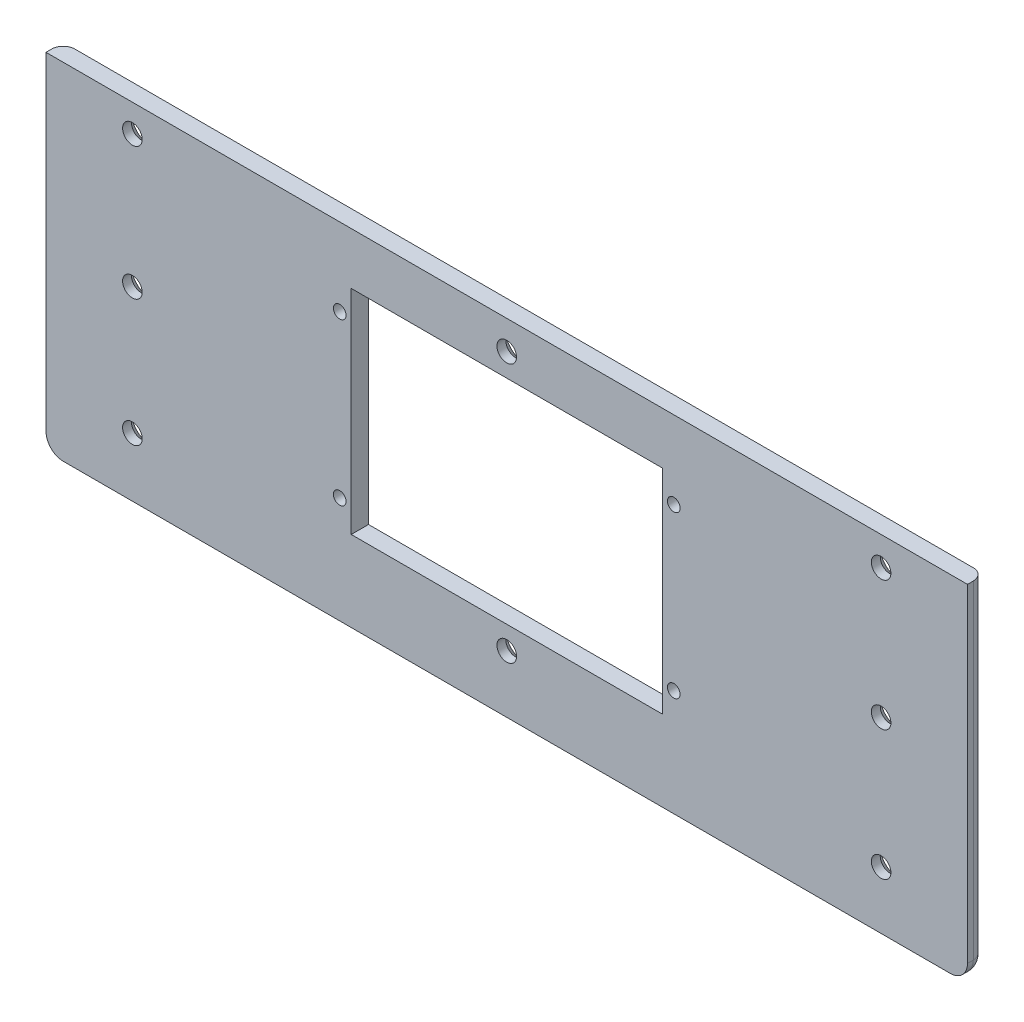
SolidWorks part; units mm, degrees
ref_plane "Front Plane" through (0, 0, 0) normal (0, 0, 1) x (1, 0, 0)
ref_plane "Top Plane" through (0, 0, 0) normal (0, 1, 0) x (1, 0, 0)
ref_plane "Right Plane" through (0, 0, 0) normal (1, 0, 0) x (0, 0, -1)
sketch "Sketch1" plane through (0, 0, 0) normal (0, 0, 1) x (1, 0, 0)
  line L1 (0, 0) -> (160, 0)
  line L2 (0, 0) -> (0, 60)
  line L3 (0, 60) -> (160, 60)
  line L4 (160, 0) -> (160, 60)
  dimension "D1" = 160
  dimension "D2" = 60
extrude "Boss-Extrude1" add sketch "Sketch1" along normal blind 3
sketch "Sketch2" plane through (0, 0, 0) normal (0, 0, -1) x (-1, 0, 0)
  line L0 (-53.5, 14.5) -> (-53.5, 50.5) construction
  line L1 (-106.5, 14.5) -> (-53.5, 14.5) construction
  line L2 (-106.5, 50.5) -> (-106.5, 14.5) construction
  line L3 (-53.5, 50.5) -> (-106.5, 50.5) construction
  line L4 (-53.5, 14.5) -> (-53.5, 50.5) construction
  line L5 (-106.5, 14.5) -> (-53.5, 14.5) construction
  line L6 (-106.5, 50.5) -> (-106.5, 14.5) construction
  line L7 (-53.5, 50.5) -> (-106.5, 50.5) construction
  line L9 (-107, 51) -> (-53, 51)
  line L10 (-107, 51) -> (-107, 14)
  line L11 (-107, 14) -> (-53, 14)
  line L12 (-53, 51) -> (-53, 14)
  circle A0 centre (-51, 18.5) radius 1.15 construction
  circle A1 centre (-51, 46.5) radius 1.15 construction
  circle A2 centre (-109, 18.5) radius 1.15 construction
  circle A3 centre (-109, 46.5) radius 1.15 construction
  circle A4 centre (-51, 18.5) radius 1.15 construction
  circle A5 centre (-51, 46.5) radius 1.15 construction
  circle A6 centre (-109, 18.5) radius 1.15 construction
  circle A7 centre (-109, 46.5) radius 1.15 construction
  circle A8 centre (-109, 46.5) radius 1.1
  circle A9 centre (-109, 18.5) radius 1.1
  circle A10 centre (-51, 18.5) radius 1.1
  circle A11 centre (-51, 46.5) radius 1.1
  dimension "D5" = 2.2
  dimension "D1" = 0.5
  dimension "D2" = 0.5
  dimension "D3" = 0.5
  dimension "D4" = 0.5
extrude "Cut-Extrude1" cut sketch "Sketch2" against normal through all
fillet "Fillet1" radius 2 3 edges at (80, 0, 0) (0, 30, 0) (160, 30, 0)
fillet "Fillet2" radius 3 4 edges at (159.4142, 0.5858, 0.5858) (0.5858, 0.5858, 0.5858) (0, 0, 2.5) (160, 0, 2.5)
sketch "Sketch4" plane through (0, 0, 0) normal (0, 0, -1) x (-1, 0, 0)
  line L0 (-80, 60) -> (-80, 55) construction
  line L1 (-158, 60) -> (-2, 60) construction
  line L2 (-80, 55) -> (-145, 55) construction
  line L3 (-145, 10) -> (-80, 10) construction
  line L4 (-80, 10) -> (-80, 55) construction
  circle A0 centre (-15, 55.2387) radius 3 construction
  circle A1 centre (-15, 32.2613) radius 3 construction
  circle A2 centre (-15, 10.2387) radius 3 construction
  circle A3 centre (-145, 10) radius 3 construction
  circle A4 centre (-145, 32.5) radius 3 construction
  circle A5 centre (-145, 55) radius 3 construction
  circle A6 centre (-15, 55.2387) radius 3
  circle A7 centre (-15, 32.2613) radius 3
  circle A8 centre (-15, 10.2387) radius 3
  circle A9 centre (-145, 10) radius 3
  circle A10 centre (-145, 32.5) radius 3
  circle A11 centre (-145, 55) radius 3
  circle A12 centre (-80, 55) radius 3
  circle A13 centre (-80, 10) radius 3
hole_wizard "CSK for M3 Flat Head Machine Screw1" positions "3DSketch1" profile "Sketch5" countersink size "M3" standard "ANSI Metric" end condition through all
sketch3d "3DSketch1"
  point P0 (145, 55, 0)
  point P3 (145, 32.5, 0)
  point P6 (145, 10, 0)
  point P9 (80, 10, 0)
  point P12 (80, 55, 0)
  point P15 (15, 55.2387, 0)
  point P18 (15, 32.2613, 0)
  point P21 (15, 10.2387, 0)
sketch "Sketch5" plane through (145, 55, 0) normal (1, 0, 0) x (0, 1, 0)
  line L0 (0, 0) -> (0, 3)
  line L1 (0, 3) -> (1.7, 3)
  line L2 (1.7, 3) -> (1.7, 1.45)
  line L3 (1.7, 1.45) -> (3.15, 0)
  line L5 (3.15, 0) -> (0, 0)
  line L6 (-1.7, 1.45) -> (-3.15, 0) construction
  line L11 (0, -6.35) -> (0, 107.95) construction
  dimension "Thru Hole Dia." = 3.4
  dimension "Thru Hole Depth" = 3
  dimension "Near C'Sink Dia." = 6.3
  dimension "Near C'Sink Angle" = 90
